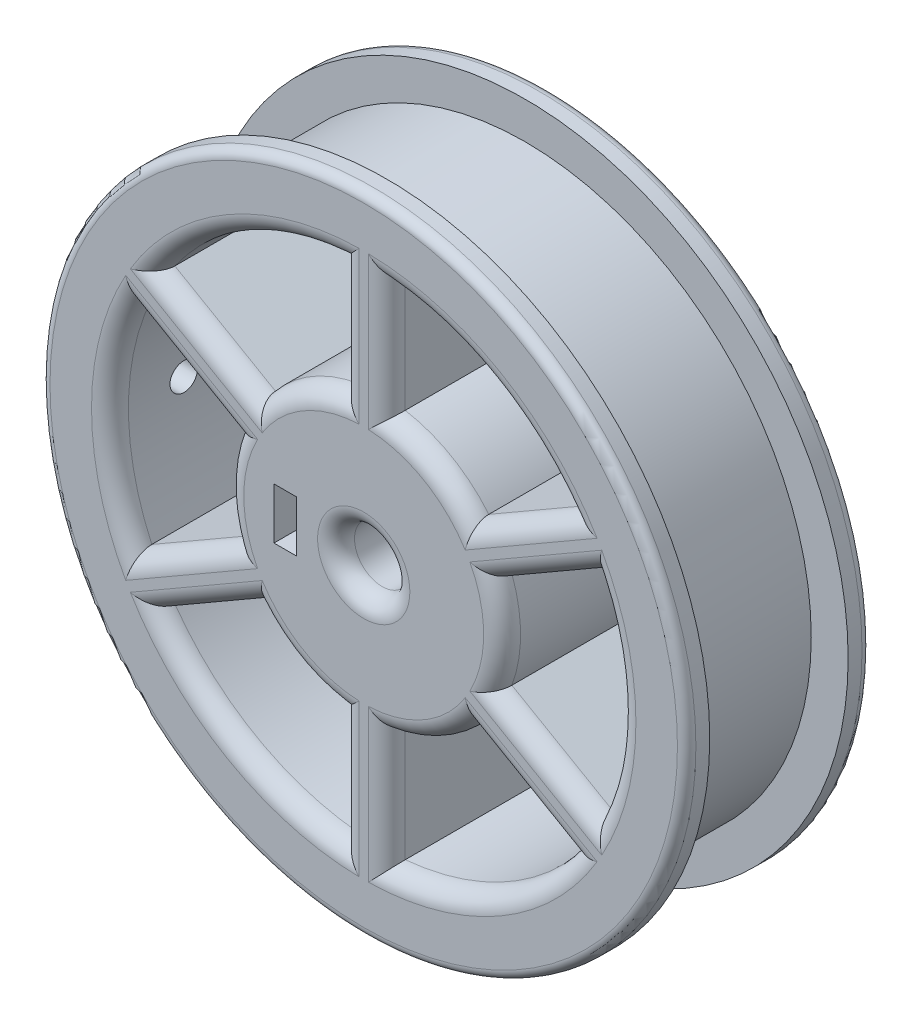
SolidWorks part; units mm, degrees
ref_plane "Front" through (0, 0, 0) normal (0, 0, 1) x (1, 0, 0)
ref_plane "Top" through (0, 0, 0) normal (0, 1, 0) x (1, 0, 0)
ref_plane "Right" through (0, 0, 0) normal (1, 0, 0) x (0, 0, -1)
sketch "Sketch1" plane through (0, 0, 0) normal (0, 0, 1) x (1, 0, 0)
  circle A0 centre (0, 0) radius 15
  circle A3 centre (0, 0) radius 3
  dimension "D1" = 30
  dimension "D2" = 6
extrude "Boss-Extrude1" add sketch "Sketch1" along normal blind 20
sketch "Sketch2" plane through (0, 0, 0) normal (0, 0, 1) x (1, 0, 0)
  circle A0 centre (0, 0) radius 35
  circle A1 centre (0, 0) radius 27.5
  dimension "D1" = 70
  dimension "D2" = 7.5
extrude "Boss-Extrude2" add sketch "Sketch2" along normal blind 20
sketch "Sketch4" plane through (0, 0, 0) normal (0, 0, 1) x (1, 0, 0)
  line L0 (0, 27.5) -> (0, 15) construction
  line L1 (0, -50) -> (0, 50) construction
  line L2 (-2.5, 27.3861) -> (-2.5, 14.7902)
  line L3 (2.5, 14.7902) -> (2.5, 27.3861)
  circle A0 centre (0, 0) radius 27.5 construction
  circle A1 centre (0, 0) radius 15 construction
  arc A2 (-2.5, 14.7902) -> (2.5, 14.7902) centre (0, 0) cw
  arc A3 (-2.5, 27.3861) -> (2.5, 27.3861) centre (0, 0) cw
  dimension "D1" = 5
extrude "Boss-Extrude3" add sketch "Sketch4" along normal up to surface (20 mm away) up to face at (35, 0, 20)
fillet "Fillet2" radius 2 2 edges at (2.5, 21.0882, 20) (-2.5, 21.0882, 20)
sketch "Sketch5" plane through (0, 0, 0) normal (1, 0, 0) x (0, 0, -1)
  line L0 (0, 0) -> (-32.2104, 0) construction
pattern_circular "CirPattern1" count 6 over 360 about axis through (0, 0, 0) along (0, 0, 1) of "Boss-Extrude3", "Fillet2" reverse direction yes
sketch "Sketch6" plane through (0, 0, 0) normal (1, 0, 0) x (0, 0, -1)
  line L0 (0, 35) -> (-20, 35) construction
  line L1 (-2.5, 35) -> (-17.5, 35)
  line L2 (-2.5, 35) -> (-2.5, 31)
  line L3 (-2.5, 31) -> (-17.5, 31)
  line L4 (-17.5, 35) -> (-17.5, 31)
  line L5 (0, -35) -> (0, 35) construction
  line L6 (-20, 35) -> (-20, -35) construction
  dimension "D1" = 2.5
  dimension "D2" = 2.5
  dimension "D3" = 4
revolve "Cut-Revolve1" cut sketch "Sketch6" angle 360 about L0
fillet "Fillet1" radius 1 2 edges at (35, 0, 0) (35, 0, 20)
fillet "Fillet3" radius 2 13 edges at (7.5, 12.9904, 20) (13.75, 23.8157, 20) (-7.5, 12.9904, 20) (-13.75, 23.8157, 20) (27.5, 0, 20) (15, 0, 20) (13.75, -23.8157, 20) (7.5, -12.9904, 20) (-13.75, -23.8157, 20) (-7.5, -12.9904, 20) (-27.5, 0, 20) (-15, 0, 20) (3, 0, 20)
sketch "Sketch7" plane through (0, 0, 0) normal (0, 0, 1) x (1, 0, 0)
  line L0 (50, 0) -> (-50, 0) construction
  line L1 (-9.725, -2.775) -> (-7.275, -2.775)
  line L2 (-9.725, -2.775) -> (-9.725, 2.775)
  line L3 (-9.725, 2.775) -> (-7.275, 2.775)
  line L4 (-7.275, -2.775) -> (-7.275, 2.775)
  line L5 (-9.725, -2.775) -> (-7.275, 2.775) construction
  line L6 (-9.725, 2.775) -> (-7.275, -2.775) construction
  point P0 (-8.5, 0)
  dimension "D1" = 5.55
  dimension "D2" = 2.45
  dimension "D3" = 8.5
extrude "Cut-Extrude1" cut sketch "Sketch7" along normal up to surface (20 mm away) up to face at (5, 0, 20)
sketch "Sketch8" plane through (0, 0, 0) normal (1, 0, 0) x (0, 0, -1)
  line L0 (0, 0) -> (-32.2104, 0) construction
  line L1 (0, 50) -> (0, -50) construction
  circle A0 centre (-6, 0) radius 1.5
  circle A1 centre (-12, 0) radius 1.5
  dimension "D1" = 3
  dimension "D2" = 6
  dimension "D3" = 6
extrude "Cut-Extrude2" cut sketch "Sketch8" against normal up to surface (31 mm away) up to face at (-31, 0, 2.5)
